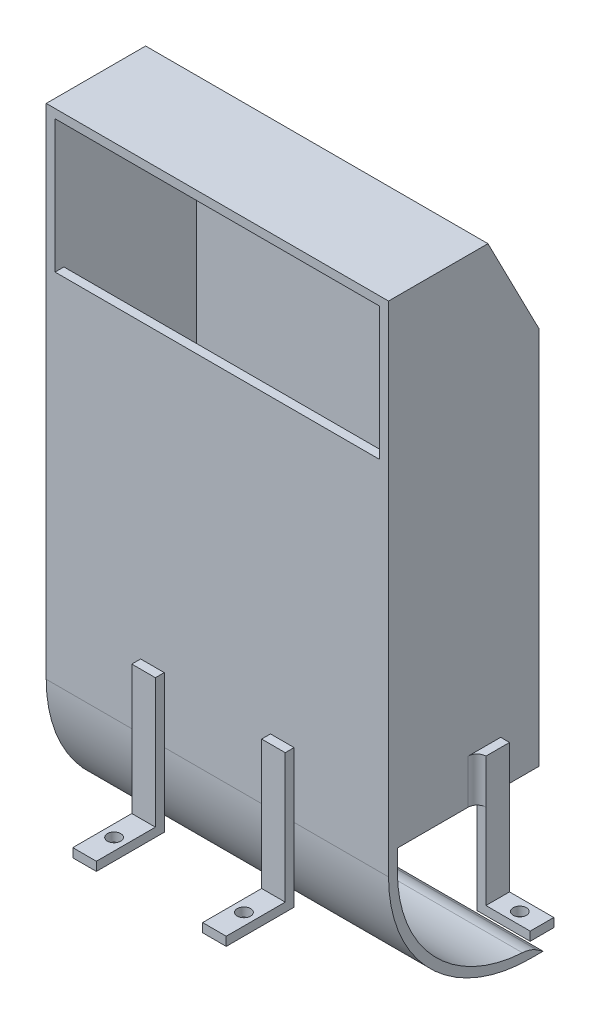
SolidWorks part; units mm, degrees
ref_plane "Front Plane" through (0, 0, 0) normal (0, 0, 1) x (1, 0, 0)
ref_plane "Top Plane" through (0, 0, 0) normal (0, 1, 0) x (1, 0, 0)
ref_plane "Right Plane" through (0, 0, 0) normal (1, 0, 0) x (0, 0, -1)
sketch "Sketch1" plane through (0, 0, 0) normal (1, 0, 0) x (0, 0, -1)
  line L0 (0, 0) -> (0, 121)
  line L1 (3, 0) -> (3, 121)
  line L2 (48, -45) -> (52.3715, -48)
  line L3 (52.3715, -48) -> (48, -48)
  line L4 (3, 121) -> (0, 121)
  arc A0 (0, 0) -> (48, -48) centre (48, 0) ccw
  arc A1 (3, 0) -> (48, -45) centre (48, 0) ccw
  dimension "D2" = 45
  dimension "D3" = 121
  dimension "D1" = 3
extrude "Boss-Extrude1" add sketch "Sketch1" along normal blind 116
sketch "Sketch2" plane through (0, 0, -3) normal (0, 0, -1) x (-1, 0, 0)
  line L1 (-116, 121) -> (-113, 121)
  line L2 (-116, 121) -> (-116, 6.9609)
  line L3 (-116, 6.9609) -> (-113, 6.9609)
  line L4 (-113, 121) -> (-113, 6.9609)
  line L5 (0, 0) -> (0, 121) construction
  line L6 (0, 121) -> (-3, 121)
  line L7 (0, 121) -> (0, 6.9609)
  line L8 (0, 6.9609) -> (-3, 6.9609)
  line L9 (-3, 121) -> (-3, 6.9609)
  line L10 (-116, 121) -> (0, 121) construction
  dimension "D1" = 3
  dimension "D2" = 3
extrude "Boss-Extrude2" add sketch "Sketch2" along normal blind 45
sketch "Sketch3" plane through (0, 0, -48) normal (0, 0, -1) x (-1, 0, 0)
  line L1 (-116, 121) -> (0, 121)
  line L2 (-116, 121) -> (-116, 6.9609)
  line L3 (-116, 6.9609) -> (0, 6.9609)
  line L4 (0, 121) -> (0, 6.9609)
extrude "Boss-Extrude3" add sketch "Sketch3" along normal blind 3
sketch "Sketch5" plane through (116, 0, 0) normal (1, 0, 0) x (0, 0, -1)
  line L0 (48, 134.156) -> (31.6048, 166)
  line L1 (51, 121) -> (51, 135.376)
  line L2 (31.6048, 166) -> (0, 166)
  line L3 (0, 166) -> (0, 169)
  line L4 (0, 169) -> (33.6883, 169)
  line L5 (33.6883, 169) -> (51, 135.376)
  line L6 (0, 121) -> (0, 0) construction
  line L7 (48, 134.156) -> (48, 121)
  line L8 (51, 121) -> (0, 121) construction
  line L9 (48, 121) -> (51, 121)
  dimension "D1" = 3
  dimension "D2" = 3
  dimension "D3" = 45
extrude "Boss-Extrude4" add sketch "Sketch5" against normal blind 116
sketch "Sketch6" plane through (116, 0, 0) normal (1, 0, 0) x (0, 0, -1)
  line L2 (0, 166) -> (31.6048, 166) construction
  line L5 (0, 166) -> (31.6048, 166)
  line L6 (0, 166) -> (0, 121)
  line L7 (48, 121) -> (0, 121) construction
  line L8 (48, 134.156) -> (48, 121) construction
  line L9 (31.6048, 166) -> (48, 134.156) construction
  line L10 (48, 121) -> (0, 121)
  line L11 (48, 134.156) -> (48, 121)
  line L12 (31.6048, 166) -> (48, 134.156)
extrude "Boss-Extrude5" add sketch "Sketch6" against normal blind 3
sketch "Sketch7" plane through (0, 0, 0) normal (-1, 0, 0) x (0, 0, 1)
  line L8 (-31.6048, 166) -> (0, 166) construction
  line L9 (-48, 134.156) -> (-31.6048, 166) construction
  line L10 (0, 166) -> (0, 121) construction
  line L11 (-31.6048, 166) -> (0, 166)
  line L12 (-48, 134.156) -> (-31.6048, 166)
  line L13 (0, 166) -> (0, 121)
  line L14 (0, 121) -> (-48, 121)
  line L15 (-48, 121) -> (-48, 134.156)
extrude "Boss-Extrude6" add sketch "Sketch7" against normal blind 3
fillet "Fillet6" radius 10 1 edges at (58, -45, -48)
sketch "Sketch8" plane through (0, 6.9609, 0) normal (0, -1, 0) x (1, 0, 0)
  line L0 (0, -51) -> (0, -3) construction
  line L1 (0, -38) -> (-3, -38)
  line L2 (0, -38) -> (0, -30)
  line L3 (0, -30) -> (-3, -30)
  line L4 (-3, -38) -> (-3, -30)
  line L5 (116, -51) -> (116, -3) construction
  line L6 (116, -30) -> (119, -30)
  line L7 (116, -30) -> (116, -38)
  line L8 (116, -38) -> (119, -38)
  line L9 (119, -30) -> (119, -38)
  line L10 (116, -51) -> (0, -51) construction
  line L11 (116, 0) -> (0, 0) construction
  line L12 (84, 0) -> (76, 0)
  line L13 (84, 0) -> (84, 3)
  line L14 (84, 3) -> (76, 3)
  line L15 (76, 0) -> (76, 3)
  line L16 (40, 0) -> (32, 0)
  line L17 (40, 0) -> (40, 3)
  line L18 (40, 3) -> (32, 3)
  line L19 (32, 0) -> (32, 3)
  line L20 (3, 0) -> (113, 0) construction
  dimension "D1" = 8
  dimension "D2" = 3
  dimension "D3" = 8
  dimension "D4" = 3
  dimension "D5" = 13
  dimension "D6" = 3
  dimension "D7" = 3
  dimension "D8" = 8
  dimension "D9" = 8
  dimension "D10" = 32
  dimension "D11" = 32
extrude "Boss-Extrude7" add sketch "Sketch8" along normal blind 31.86 and the other way blind 15
sketch "Sketch9" plane through (-3, 0, 0) normal (-1, 0, 0) x (0, 0, 1)
  line L0 (-30, 21.9609) -> (-30, -24.8991) construction
  line L1 (-38, -24.8991) -> (-30, -24.8991)
  line L2 (-38, -24.8991) -> (-38, -21.8991)
  line L3 (-38, -21.8991) -> (-30, -21.8991)
  line L4 (-30, -24.8991) -> (-30, -21.8991)
  dimension "D1" = 3
extrude "Boss-Extrude8" add sketch "Sketch9" along normal blind 15
sketch "Sketch10" plane through (119, 0, 0) normal (1, 0, 0) x (0, 0, -1)
  line L0 (38, 21.9609) -> (38, -24.8991) construction
  line L1 (30, -24.8991) -> (38, -24.8991)
  line L2 (30, -24.8991) -> (30, -21.8991)
  line L3 (30, -21.8991) -> (38, -21.8991)
  line L4 (38, -24.8991) -> (38, -21.8991)
  dimension "D1" = 3
extrude "Boss-Extrude9" add sketch "Sketch10" along normal blind 15
sketch "Sketch11" plane through (0, -21.8991, 0) normal (0, 1, 0) x (1, 0, 0)
  line L1 (-18, 30) -> (-3, 30) construction
  line L2 (134, 30) -> (119, 30) construction
  line L3 (134, 38) -> (134, 30) construction
  circle A0 centre (126.5, 34) radius 2.25
  circle A1 centre (-10.5, 33.6325) radius 2.25
  point P8 (-10.5, 30)
  point P14 (126.5, 30)
  point P17 (134, 34)
  dimension "D1" = 4.5
  dimension "D2" = 4.5
extrude "Cut-Extrude1" cut sketch "Sketch11" against normal blind 15
sketch "Sketch12" plane through (0, 0, 3) normal (0, 0, 1) x (1, 0, 0)
  line L0 (32, 21.9609) -> (32, -24.8991) construction
  line L1 (40, -24.8991) -> (32, -24.8991)
  line L2 (40, -24.8991) -> (40, -21.8991)
  line L3 (40, -21.8991) -> (32, -21.8991)
  line L4 (32, -24.8991) -> (32, -21.8991)
  line L5 (84, 21.9609) -> (84, -24.8991) construction
  line L6 (76, -24.8991) -> (84, -24.8991)
  line L7 (76, -24.8991) -> (76, -21.8991)
  line L8 (76, -21.8991) -> (84, -21.8991)
  line L9 (84, -24.8991) -> (84, -21.8991)
  dimension "D1" = 3
  dimension "D2" = 3
extrude "Boss-Extrude10" add sketch "Sketch12" along normal blind 20
sketch "Sketch13" plane through (0, -21.8991, 0) normal (0, 1, 0) x (1, 0, 0)
  line L0 (40, -23) -> (40, -3) construction
  line L1 (40, -23) -> (32, -23) construction
  line L2 (84, -23) -> (76, -23) construction
  line L3 (84, -23) -> (84, -3) construction
  circle A0 centre (36, -13) radius 2.25
  circle A1 centre (80, -13) radius 2.25
  point P6 (40, -13)
  point P9 (36, -23)
  point P12 (80, -23)
  point P15 (84, -13)
  dimension "D1" = 4.5
  dimension "D2" = 4.5
extrude "Cut-Extrude2" cut sketch "Sketch13" against normal blind 20
fillet "Fillet7" radius 3 2 edges at (116, 14.4609, -30) (0, 14.4609, -30)
